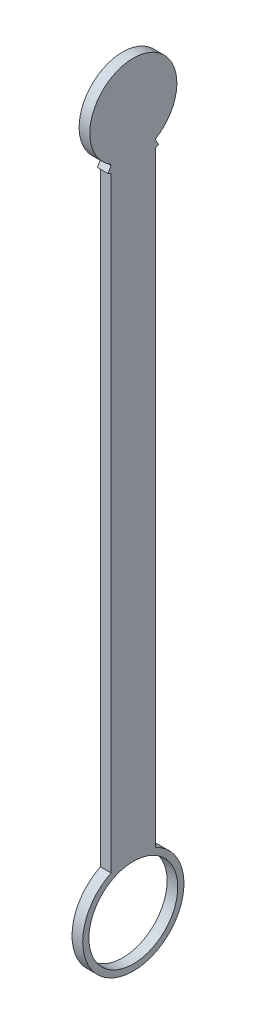
SolidWorks part; units mm, degrees
ref_plane "Front Plane" through (0, 0, 0) normal (0, 0, 1) x (1, 0, 0)
ref_plane "Top Plane" through (0, 0, 0) normal (0, 1, 0) x (1, 0, 0)
ref_plane "Right Plane" through (0, 0, 0) normal (1, 0, 0) x (0, 0, -1)
sketch "Sketch1" plane through (0, 0, 0) normal (1, 0, 0) x (0, 0, -1)
  line L0 (0, -196) -> (0, 196)
  line L1 (12.5, 196) -> (-12.5, 196)
  line L2 (-12.5, 196) -> (-12.5, -196)
  line L3 (-12.5, -196) -> (12.5, -196)
  line L4 (12.5, -196) -> (12.5, 196)
  line L7 (-37.2876, 196) -> (28.5, 196) construction
  line L8 (-12.5, 174.3494) -> (-14.25, 171.3183)
  line L9 (12.5, 174.3494) -> (14.25, 171.3183)
  circle A1 centre (0, -196) radius 28.5
  circle A3 centre (0, 196) radius 24.5
  arc A6 (-14.25, 171.3183) -> (14.25, 171.3183) centre (0, 196) ccw
  point P4 (0, 0)
  point P10 (0, 196)
  dimension "D2" = 49
  dimension "D3" = 57
  dimension "D5" = 57
  dimension "D1" = 392
  dimension "D4" = 25
  dimension "D6" = 60
extrude "Boss-Extrude1" add sketch "Sketch1" along normal mid plane 6 contours L4 L2 L1 | L0 L4 L1 | L2 L0 L1 | A1 L0 L2 | A1 L4 L0 | L4 A1 L0 L3 | L0 A1 L2 L3 | L2 A1 L4 L3 | L2 | L4 | L7 L4 | L7 L2 | L2 L0 | L0 L4 region at (0, -182.2078, 6.1421) region at (0, -201.1009, 0) region at (0, -182.2078, -6.1421) region at (0, 0, 6.2677) region at (0, 0, -6.2677) region at (0, 170.5605, 6.3798) region at (0, 170.5605, -6.3798) region at (0, 184.2826, 6.0997) region at (0, 184.2826, -6.0997) region at (0, 172.0107, 13.0853) region at (0, 172.0107, -13.0853) region at (0, 201.2669, 0)
sketch "Sketch2" plane through (3, 0, 0) normal (1, 0, 0) x (0, 0, -1)
  circle A0 centre (0, -196) radius 25
  dimension "D1" = 50
extrude "Cut-Extrude1" cut sketch "Sketch2" against normal through all
